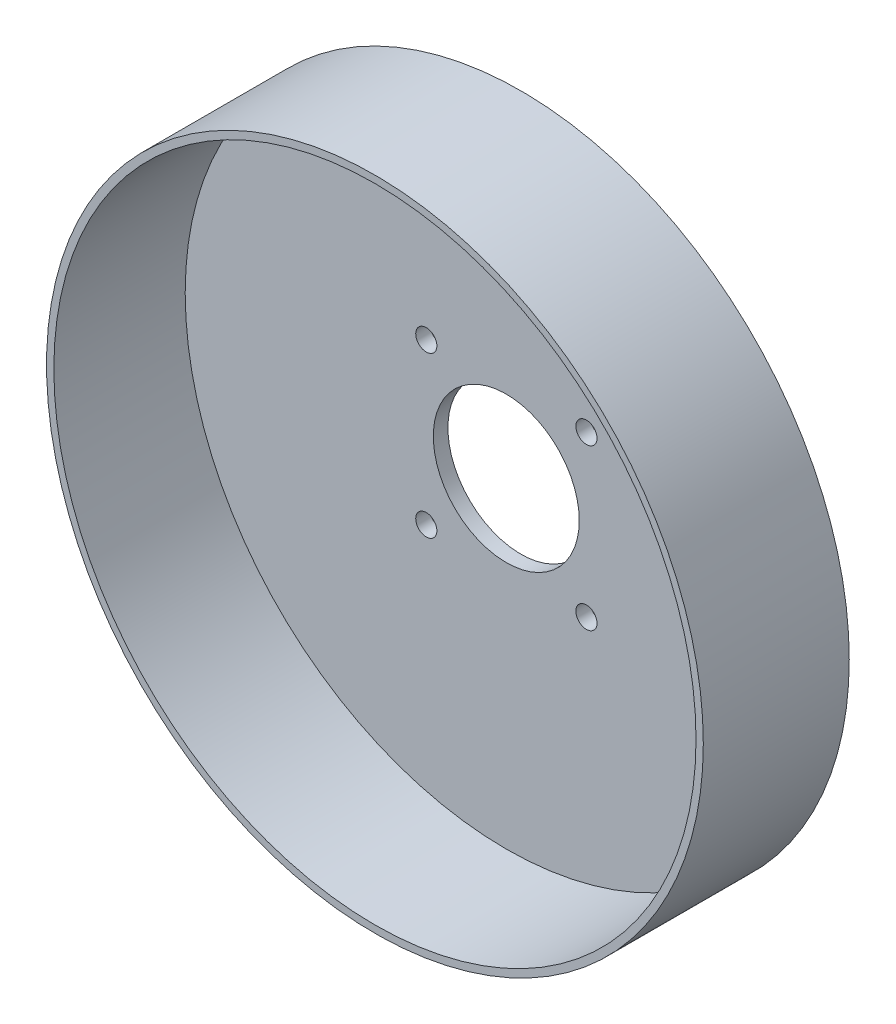
SolidWorks part; units mm, degrees
note: The reader was unsure of these and kept them because the rebuilt part matched: shared geometry of "Sketch1<2>".
ref_plane "Front Plane" through (0, 0, 0) normal (0, 0, 1) x (1, 0, 0)
ref_plane "Top Plane" through (0, 0, 0) normal (0, 1, 0) x (1, 0, 0)
ref_plane "Right Plane" through (0, 0, 0) normal (1, 0, 0) x (0, 0, -1)
sketch "Sketch1" plane through (0, 0, 0) normal (0, 0, 1) x (1, 0, 0)
  circle A0 centre (0, 0) radius 45
  circle A1 centre (0, 0) radius 44
  dimension "D1" = 90
  dimension "D2" = 88
extrude "Boss-Extrude1" add sketch "Sketch1" along normal blind 18
extrude "Boss-Extrude2" add sketch "Sketch1<2>" against normal blind 2 contours A1 | A0 A1
sketch "Sketch1<2>" plane through (0, 0, 0) normal (0, 0, 1) x (1, 0, 0) same geometry as "Sketch1"
sketch "Sketch2" plane through (0, 0, -2) normal (0, 0, -1) x (-1, 0, 0)
  line L0 (0, 0) -> (15.5, 0) construction
  line L1 (0, 0) -> (10.9602, 10.9602) construction
  circle A0 centre (0, 0) radius 15.5 construction
  circle A1 centre (0, 0) radius 10
  dimension "D1" = 31
  dimension "D3" = 20
  dimension "D2" = 45
hole_wizard "M3.5x0.6 Tapped Hole1" positions "Sketch3" profile "Sketch4" tap size "M3.5x0.6" standard "ANSI Metric" end condition through all
sketch "Sketch3" plane through (0, 0, -2) normal (0, 0, -1) x (-1, 0, 0)
  point P0 (10.9602, 10.9602)
sketch "Sketch4" plane through (-10.9602, 10.9602, -2) normal (1, 0, 0) x (0, 1, 0)
  line L0 (0, 0) -> (0, 20)
  line L1 (0, 20) -> (1.45, 20)
  line L2 (1.45, 20) -> (1.45, 0)
  line L5 (1.45, 0) -> (0, 0)
  line L11 (0, -6.35) -> (0, 107.95) construction
  dimension "Thru Tap Drill Dia." = 2.9
  dimension "Thru Tap Drill Depth" = 20
cosmetic thread "Hole Thread1"
pattern_circular "CirPattern1" count 4 over 360 about axis through (0.0114, -0.0114, 0) along (0, 0, 1) of "M3.5x0.6 Tapped Hole1"
cosmetic thread "Hole Thread2"
cosmetic thread "Hole Thread3"
cosmetic thread "Hole Thread4"
extrude "Cut-Extrude1" cut sketch "Sketch2" against normal through all both and the other way through all contours A1
